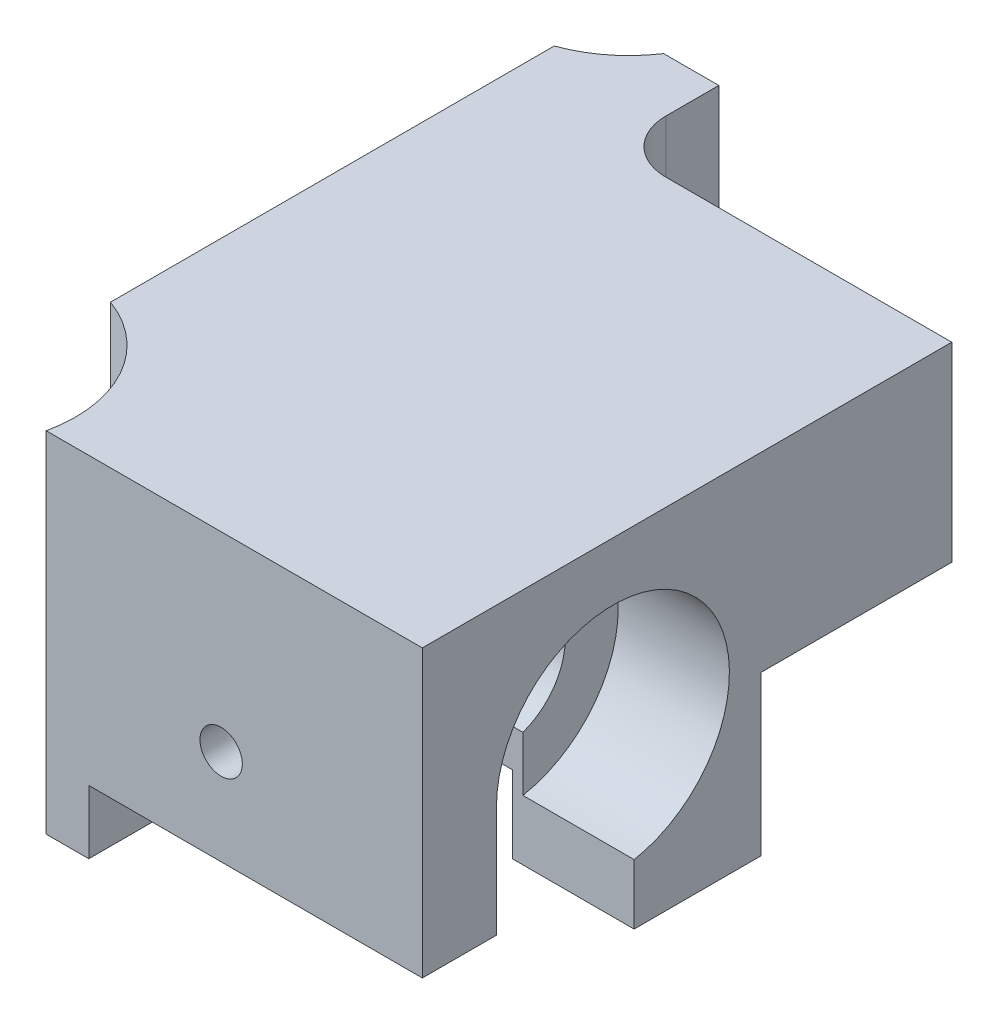
SolidWorks part; units mm, degrees
ref_plane "Front Plane" through (0, 0, 0) normal (0, 0, 1) x (1, 0, 0)
ref_plane "Top Plane" through (0, 0, 0) normal (0, 1, 0) x (1, 0, 0)
ref_plane "Right Plane" through (0, 0, 0) normal (1, 0, 0) x (0, 0, -1)
sketch "Sketch1" plane through (0, 0, 0) normal (0, 0, 1) x (1, 0, 0)
  line L1 (19, -15) -> (-24, -15)
  line L2 (19, -15) -> (19, 18)
  line L3 (19, 18) -> (-24, 18)
  line L4 (-24, -15) -> (-24, 18)
  circle A0 centre (0, 0) radius 2
  dimension "D1" = 33
  dimension "D3" = 24
  dimension "D4" = 19
  dimension "D5" = 4
  dimension "D2" = 15
extrude "Boss-Extrude1" add sketch "Sketch1" along normal blind 60
sketch "Sketch2" plane through (-24, 0, 0) normal (-1, 0, 0) x (0, 0, 1)
  line L0 (10, 18) -> (10, -15) construction
  line L1 (60, 18) -> (0, 18) construction
  line L2 (60, -15) -> (0, -15) construction
  line L3 (27.5, 18) -> (27.5, -15) construction
  line L4 (0, 1.5) -> (60, 1.5) construction
  line L5 (60, 18) -> (60, -15) construction
  line L6 (0, 18) -> (0, -15) construction
  circle A0 centre (27.5, 9.75) radius 1.75
  circle A1 centre (27.5, -6.75) radius 1.75
  circle A2 centre (10, -6.75) radius 1.75
  circle A3 centre (10, 9.75) radius 1.75
  dimension "D2" = 3.5
  dimension "D3" = 8.25
  dimension "D4" = 8.25
  dimension "D5" = 8.25
  dimension "D6" = 8.25
  dimension "D1" = 17.5
  dimension "D7" = 10
extrude "Cut-Extrude1" cut sketch "Sketch2" against normal blind 5
sketch "Sketch3" plane through (0, -15, 0) normal (0, -1, 0) x (1, 0, 0)
  line L0 (-28, -6.5) -> (-28, 57.5) construction
  line L1 (-24, 60) -> (-24, 0) construction
  line L2 (-24, 0) -> (19, 0) construction
  circle A0 centre (-28, 57.5) radius 11.75
  circle A1 centre (-28, -6.5) radius 11.75
  dimension "D4" = 23.5
  dimension "D1" = 4
  dimension "D2" = 64
  dimension "D3" = 6.5
extrude "Cut-Extrude2" cut sketch "Sketch3" against normal up to surface (33 mm away) up to face at (-2.5, 18, 30)
sketch "Sketch4" plane through (-24, 0, 0) normal (-1, 0, 0) x (0, 0, 1)
  line L0 (0, 1.5) -> (60, 1.5) construction
  line L2 (10, -6.75) -> (10, 9.75) construction
  line L3 (60, -15) -> (60, 18) construction
  circle A0 centre (42, 1.5) radius 4.5
  dimension "D1" = 32
extrude "Cut-Extrude3" cut sketch "Sketch4" against normal up to surface (43 mm away) up to face at (19, 1.5, 30)
ref_axis "Axis1" through (0, 0, 60) along (0, 0, -1)
ref_plane "Plane1" through (0, 0, 0) normal (-1, 0, 0) x (0, 0, 1)
sketch "Sketch5" plane through (0, 0, 0) normal (-1, 0, 0) x (0, 0, 1)
  circle A0 centre (42, 1.5) radius 6
  dimension "D1" = 12
extrude "Cut-Extrude4" cut sketch "Sketch5" against normal blind 8.5 and the other way blind 8.5
sketch "Sketch6" plane through (19, 0, 0) normal (1, 0, 0) x (0, 0, -1)
  circle A0 centre (-42, 1.5) radius 11
extrude "Cut-Extrude5" cut sketch "Sketch6" against normal up to surface (10.5 mm away) up to face at (8.5, -4.5, 42)
sketch "Sketch8" plane through (0, 0, 0) normal (-1, 0, 0) x (0, 0, 1)
  line L0 (0, 0) -> (33.8998, 0) construction
  line L1 (28, 0) -> (28, 8.25)
  line L2 (28, 8.25) -> (23.3, 8.25)
  line L3 (23.3, 8.25) -> (23.3, 6)
  line L4 (23.3, 6) -> (18.7, 6)
  line L5 (15.7, 6) -> (15.7, 8.25)
  line L6 (15.7, 8.25) -> (18.7, 8.25)
  line L7 (18.7, 8.25) -> (18.7, 6)
  line L8 (15.7, 6) -> (0, 6)
  line L9 (0, -15) -> (0, 18) construction
  line L10 (0, 6) -> (0, 0)
  line L11 (0, 0) -> (28, 0)
  dimension "D1" = 8.25
  dimension "D2" = 4.7
  dimension "D3" = 4.6
  dimension "D4" = 3
  dimension "D5" = 6
  dimension "D6" = 28
revolve "Cut-Revolve1" cut sketch "Sketch8" angle 360 about L0
sketch "Sketch10" plane through (0, -15, 0) normal (0, -1, 0) x (1, 0, 0)
  line L0 (-8.25, 28) -> (8.25, 28) construction
  line L1 (19, 0) -> (-13, 0)
  line L2 (19, 0) -> (19, 10)
  line L3 (19, 10) -> (-13, 10)
  line L4 (-13, 0) -> (-13, 10)
  dimension "D1" = 32
  dimension "D2" = 18
extrude "Cut-Extrude6" cut sketch "Sketch10" against normal up to surface (33 mm away) up to face at (-6.9699, 18, 28.3432)
sketch "Sketch16" plane through (19, 0, 0) normal (1, 0, 0) x (0, 0, -1)
  line L0 (-28, -8.25) -> (-28, 8.25) construction
  line L1 (-28, 0) -> (-10, 0)
  line L2 (-28, 0) -> (-28, -15)
  line L3 (-28, -15) -> (-10, -15)
  line L4 (-10, 0) -> (-10, -15)
extrude "Cut-Extrude9" cut sketch "Sketch16" against normal offset from surface (36.5 mm away) 4.5 up to face at (-13, 1.5, 5) offset beyond the face yes
sketch "Sketch17" plane through (19, 0, 0) normal (1, 0, 0) x (0, 0, -1)
  line L0 (-60, -15) -> (-28, -15) construction
  line L1 (-40, -15) -> (-57, -15)
  line L2 (-40, -15) -> (-40, 10.0784)
  line L3 (-40, 10.0784) -> (-48.8856, 10.0784)
  line L5 (-52.9995, -9) -> (-53, 1.4995)
  line L6 (-60, -15) -> (-60, 18) construction
  line L7 (-52.9995, -9) -> (-60, -9)
  line L8 (-60, -9) -> (-60, -15)
  line L9 (-60, -15) -> (-57, -15)
  arc A0 (-48.8856, 10.0784) -> (-53, 1.4995) centre (-42, 1.5) ccw
  dimension "D1" = 20
  dimension "D2" = 6
extrude "Cut-Extrude10" cut sketch "Sketch17" against normal blind 31.5
sketch "Sketch18" plane through (0, 0, 0) normal (-1, 0, 0) x (0, 0, 1)
  line L0 (42, 1.5) -> (42, -11.75) construction
  line L1 (60, 0) -> (44.6803, 0) construction
  line L2 (31, -11.75) -> (31, -22.75)
  line L3 (31, -22.75) -> (42, -22.75)
  arc A0 (42, -22.75) -> (31, -11.75) centre (42, -11.75) ccw
  dimension "D1" = 22
  dimension "D2" = 11.75
extrude "Cut-Extrude11" cut sketch "Sketch18" against normal blind 6 and the other way blind 6
sketch "Sketch19" plane through (0, 0, 0) normal (0, -1, 0) x (1, 0, 0)
  line L0 (13, 10) -> (13, 28) construction
  line L3 (19, 10) -> (19, 28) construction
  circle A0 centre (13, 19) radius 1.75
  dimension "D1" = 3.5
  dimension "D2" = 6
extrude "Cut-Extrude12" cut sketch "Sketch19" against normal blind 6
sketch "Sketch20" plane through (0, 0, 0) normal (0, -1, 0) x (1, 0, 0)
  line L0 (19, 10) -> (6, 10) construction
  line L1 (11.4845, 16.375) -> (14.5155, 16.375)
  line L2 (14.5155, 16.375) -> (16.0311, 19)
  line L3 (16.0311, 19) -> (14.5155, 21.625)
  line L4 (14.5155, 21.625) -> (11.4845, 21.625)
  line L5 (11.4845, 21.625) -> (9.9689, 19)
  line L6 (9.9689, 19) -> (11.4845, 16.375)
  circle A0 centre (13, 19) radius 2.625 construction
  dimension "D1" = 5.25
extrude "Cut-Extrude13" cut sketch "Sketch20" against normal blind 2.5
mirror "Mirror1" about plane through (0, 0, 0) normal (-1, 0, 0) of "Cut-Extrude13", "Cut-Extrude12"
sketch "Sketch21" plane through (-24, 0, 0) normal (-1, 0, 0) x (0, 0, 1)
  line L1 (30.125, 8.2345) -> (30.125, 11.2655)
  line L2 (30.125, 11.2655) -> (27.5, 12.7811)
  line L3 (27.5, 12.7811) -> (24.875, 11.2655)
  line L4 (24.875, 11.2655) -> (24.875, 8.2345)
  line L5 (24.875, 8.2345) -> (27.5, 6.7189)
  line L6 (27.5, 6.7189) -> (30.125, 8.2345)
  line L7 (12.625, 8.2345) -> (12.625, 11.2655)
  line L8 (12.625, 11.2655) -> (10, 12.7811)
  line L9 (10, 12.7811) -> (7.375, 11.2655)
  line L10 (7.375, 11.2655) -> (7.375, 8.2345)
  line L11 (7.375, 8.2345) -> (10, 6.7189)
  line L12 (10, 6.7189) -> (12.625, 8.2345)
  line L13 (12.625, -8.2655) -> (12.625, -5.2345)
  line L14 (12.625, -5.2345) -> (10, -3.7189)
  line L15 (10, -3.7189) -> (7.375, -5.2345)
  line L16 (7.375, -5.2345) -> (7.375, -8.2655)
  line L17 (7.375, -8.2655) -> (10, -9.7811)
  line L18 (10, -9.7811) -> (12.625, -8.2655)
  line L19 (0, -15) -> (0, 18) construction
  line L20 (30.125, -8.2655) -> (30.125, -5.2345)
  line L21 (30.125, -5.2345) -> (27.5, -3.7189)
  line L22 (27.5, -3.7189) -> (24.875, -5.2345)
  line L23 (24.875, -5.2345) -> (24.875, -8.2655)
  line L24 (24.875, -8.2655) -> (27.5, -9.7811)
  line L25 (27.5, -9.7811) -> (30.125, -8.2655)
  circle A0 centre (27.5, 9.75) radius 2.625 construction
  circle A1 centre (10, 9.75) radius 2.625 construction
  circle A2 centre (10, -6.75) radius 2.625 construction
  circle A3 centre (27.5, -6.75) radius 2.625 construction
  dimension "D1" = 5.25
extrude "Cut-Extrude14" cut sketch "Sketch21" against normal blind 2.5
fillet "Fillet1" radius 5 1 edges at (-13, 9, 10)
sketch "Sketch23" plane through (0, 0, 0) normal (1, 0, 0) x (0, 0, -1)
  line L0 (-42, -11.75) -> (-42, -14.25) construction
  line L1 (-37.5, -11.75) -> (-37.5, -14.25)
  line L2 (-46.5, -11.75) -> (-46.5, -14.25)
  arc A0 (-37.5, -11.75) -> (-46.5, -11.75) centre (-42, -11.75) ccw
  arc A1 (-46.5, -14.25) -> (-37.5, -14.25) centre (-42, -14.25) ccw
  point P2 (-42, -13)
  dimension "D1" = 4.5
  dimension "D2" = 2.5
extrude "Cut-Extrude16" cut sketch "Sketch23" against normal blind 7.5 and the other way blind 7.5
sketch "Sketch24" plane through (0, -9, 0) normal (0, -1, 0) x (1, 0, 0)
  line L0 (19, 56.4998) -> (-12.5, 56.4998) construction
  line L1 (19, 52.9995) -> (19, 60) construction
  line L2 (-12.5, 60) -> (-12.5, 40) construction
  line L3 (-12.5, 60) -> (19, 60) construction
  line L4 (14.4434, 53.9998) -> (15.8868, 56.4998)
  line L5 (15.8868, 56.4998) -> (14.4434, 58.9998)
  line L6 (14.4434, 58.9998) -> (11.5566, 58.9998)
  line L7 (11.5566, 58.9998) -> (10.1132, 56.4998)
  line L8 (10.1132, 56.4998) -> (11.5566, 53.9998)
  line L9 (11.5566, 53.9998) -> (14.4434, 53.9998)
  circle A0 centre (13, 56.4998) radius 2.5 construction
  circle A1 centre (13, 19) radius 1.75 construction
  dimension "D1" = 5
  dimension "D2" = 0
extrude "Cut-Extrude17" cut sketch "Sketch24" against normal blind 3
sketch "Sketch25" plane through (0, -9, 0) normal (0, -1, 0) x (1, 0, 0)
  line L0 (-12.5, 56.4998) -> (19, 56.4998) construction
  line L1 (-12.5, 60) -> (-12.5, 40) construction
  line L2 (19, 52.9995) -> (19, 60) construction
  circle A0 centre (13, 56.4998) radius 1.75
  circle A1 centre (13, 19) radius 1.75 construction
  dimension "D1" = 3.5
  dimension "D2" = 0
extrude "Cut-Extrude18" cut sketch "Sketch25" against normal blind 5
sketch "Sketch26" plane through (0, -15, 0) normal (0, -1, 0) x (1, 0, 0)
  line L0 (19, 34) -> (-24, 34) construction
  line L1 (19, 40) -> (19, 28) construction
  line L2 (-24, 46.4518) -> (-24, 4.5482) construction
  circle A0 centre (13, 34) radius 1.75
  circle A1 centre (-13, 34) radius 1.75
  circle A2 centre (13, 19) radius 1.75 construction
  circle A3 centre (-13, 19) radius 1.75 construction
  dimension "D1" = 3.5
  dimension "D2" = 0
  dimension "D3" = 0
extrude "Cut-Extrude19" cut sketch "Sketch26" against normal blind 5
sketch "Sketch27" plane through (0, -15, 0) normal (0, -1, 0) x (1, 0, 0)
  line L0 (-17.5, 28) -> (19, 28) construction
  line L1 (14.4434, 31.5) -> (15.8868, 34)
  line L2 (15.8868, 34) -> (14.4434, 36.5)
  line L3 (14.4434, 36.5) -> (11.5566, 36.5)
  line L4 (11.5566, 36.5) -> (10.1132, 34)
  line L5 (10.1132, 34) -> (11.5566, 31.5)
  line L6 (11.5566, 31.5) -> (14.4434, 31.5)
  line L7 (-10.1132, 34) -> (-11.5566, 36.5)
  line L8 (-11.5566, 36.5) -> (-14.4434, 36.5)
  line L9 (-14.4434, 36.5) -> (-15.8868, 34)
  line L10 (-15.8868, 34) -> (-14.4434, 31.5)
  line L11 (-14.4434, 31.5) -> (-11.5566, 31.5)
  line L12 (-11.5566, 31.5) -> (-10.1132, 34)
  circle A0 centre (13, 34) radius 2.5 construction
  circle A1 centre (-13, 34) radius 2.5 construction
  dimension "D1" = 5
extrude "Cut-Extrude20" cut sketch "Sketch27" against normal blind 3
sketch "Sketch28" plane through (-8.5, 0, 0) normal (1, 0, 0) x (0, 0, -1)
  circle A0 centre (-42, 1.5) radius 11
extrude "Cut-Extrude21" cut sketch "Sketch28" against normal blind 7
